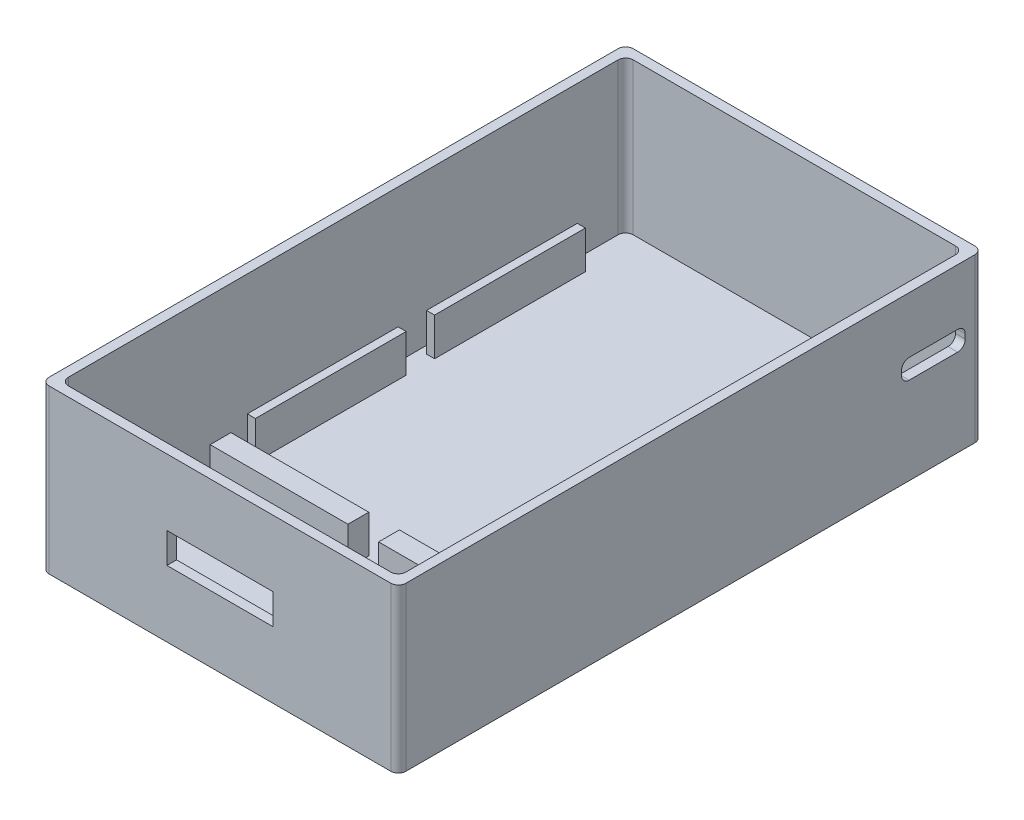
SolidWorks part; units mm, degrees
ref_plane "Front Plane" through (0, 0, 0) normal (0, 0, 1) x (1, 0, 0)
ref_plane "Top Plane" through (0, 0, 0) normal (0, 1, 0) x (1, 0, 0)
ref_plane "Right Plane" through (0, 0, 0) normal (1, 0, 0) x (0, 0, -1)
sketch "Sketch1" plane through (0, 0, 0) normal (0, 1, 0) x (1, 0, 0)
  line L5 (0, 0) -> (47.0912, 0)
  line L6 (0, 0) -> (0, -77.0912)
  line L7 (0, -77.0912) -> (47.0912, -77.0912)
  line L8 (47.0912, 0) -> (47.0912, -77.0912)
extrude "Boss-Extrude1" add sketch "Sketch1" along normal blind 1.5
sketch "Sketch2" plane through (0, 1.5, 0) normal (0, 1, 0) x (1, 0, 0)
  line L3 (1.2728, -1.2728) -> (45.8184, -1.2728)
  line L4 (1.2728, -1.2728) -> (1.2728, -75.8184)
  line L5 (1.2728, -75.8184) -> (45.8184, -75.8184)
  line L6 (45.8184, -1.2728) -> (45.8184, -75.8184)
  line L7 (0, 0) -> (47.0912, 0)
  line L8 (0, 0) -> (0, -77.0912)
  line L9 (0, -77.0912) -> (47.0912, -77.0912)
  line L10 (47.0912, 0) -> (47.0912, -77.0912)
extrude "Boss-Extrude2" add sketch "Sketch2" along normal blind 20
fillet "Fillet4" radius 1 8 edges at (45.8184, 11.5, 1.2728) (1.2728, 11.5, 1.2728) (45.8184, 11.5, 75.8184) (1.2728, 11.5, 75.8184) (47.0912, 10.75, 0) (0, 10.75, 0) (47.0912, 10.75, 77.0912) (0, 10.75, 77.0912)
sketch "Sketch3" plane through (0, 1.5, 0) normal (0, 1, 0) x (1, 0, 0)
  line L1 (2.2728, -2.2728) -> (44.8184, -2.2728)
  line L2 (2.2728, -2.2728) -> (2.2728, -74.8184)
  line L3 (2.2728, -74.8184) -> (44.8184, -74.8184)
  line L4 (44.8184, -2.2728) -> (44.8184, -74.8184)
sketch "Sketch9" plane through (47.0912, 0, 0) normal (1, 0, 0) x (0, 0, -1)
  line L1 (-10.6728, 11.5) -> (-2.2728, 11.5)
  line L2 (-10.6728, 11.5) -> (-10.6728, 14.1)
  line L3 (-10.6728, 14.1) -> (-2.2728, 14.1)
  line L4 (-2.2728, 11.5) -> (-2.2728, 14.1)
  line L6 (-2.2728, 11.5) -> (-10.3106, 11.5)
extrude "Cut-Extrude4" cut sketch "Sketch9" against normal blind 2 contours L1 L4 L3 L2 region at (47.0912, 12.8, 6.4728)
fillet "Fillet5" radius 1 4 edges at (46.4548, 14.1, 10.6728) (46.4548, 11.5, 2.2728) (46.4548, 14.1, 2.2728) (46.4548, 11.5, 10.6728)
sketch "Sketch10" plane through (0, 1.5, 0) normal (0, 1, 0) x (1, 0, 0)
  line L5 (3.3356, -58.1743) -> (21.5231, -58.1743)
  line L6 (3.3356, -58.1743) -> (3.3356, -55.4274)
  line L7 (3.3356, -55.4274) -> (21.5231, -55.4274)
  line L8 (21.5231, -58.1743) -> (21.5231, -55.4274)
  line L10 (25.5681, -58.1743) -> (25.5681, -55.4274)
  line L11 (43.7555, -55.4274) -> (25.5681, -55.4274)
  line L12 (43.7555, -58.1743) -> (43.7555, -55.4274)
  line L13 (43.7555, -58.1743) -> (25.5681, -58.1743)
  line L14 (2.2728, -2.2728) -> (2.2728, -74.8184) construction
  line L15 (3.3356, -52.1993) -> (2.2728, -52.1993)
  line L16 (3.3356, -52.1993) -> (3.3356, -32.3037)
  line L17 (3.3356, -32.3037) -> (2.2728, -32.3037)
  line L18 (2.2728, -52.1993) -> (2.2728, -32.3037)
  line L20 (2.2728, -8.6554) -> (2.2728, -28.551)
  line L21 (3.3356, -28.551) -> (2.2728, -28.551)
  line L22 (3.3356, -8.6554) -> (3.3356, -28.551)
  line L23 (3.3356, -8.6554) -> (2.2728, -8.6554)
  line L24 (43.7555, -8.6554) -> (44.8184, -8.6554)
  line L25 (43.7555, -8.6554) -> (43.7555, -28.551)
  line L26 (43.7555, -28.551) -> (44.8184, -28.551)
  line L27 (44.8184, -8.6554) -> (44.8184, -28.551)
  line L28 (44.8184, -52.1993) -> (44.8184, -32.3037)
  line L29 (43.7555, -32.3037) -> (44.8184, -32.3037)
  line L30 (43.7555, -52.1993) -> (43.7555, -32.3037)
  line L31 (43.7555, -52.1993) -> (44.8184, -52.1993)
extrude "Boss-Extrude4" add sketch "Sketch10" along normal blind 5
sketch "Sketch11" plane through (0, 0, 77.0912) normal (0, 0, 1) x (1, 0, 0)
  line L2 (16.5456, 12.7566) -> (16.5456, 8.7566)
  line L7 (16.5456, 12.7566) -> (30.5456, 12.7566)
  line L9 (16.5456, 8.7566) -> (30.5456, 8.7566)
  line L10 (30.5456, 12.7566) -> (30.5456, 8.7566)
extrude "Cut-Extrude5" cut sketch "Sketch11" against normal blind 10
